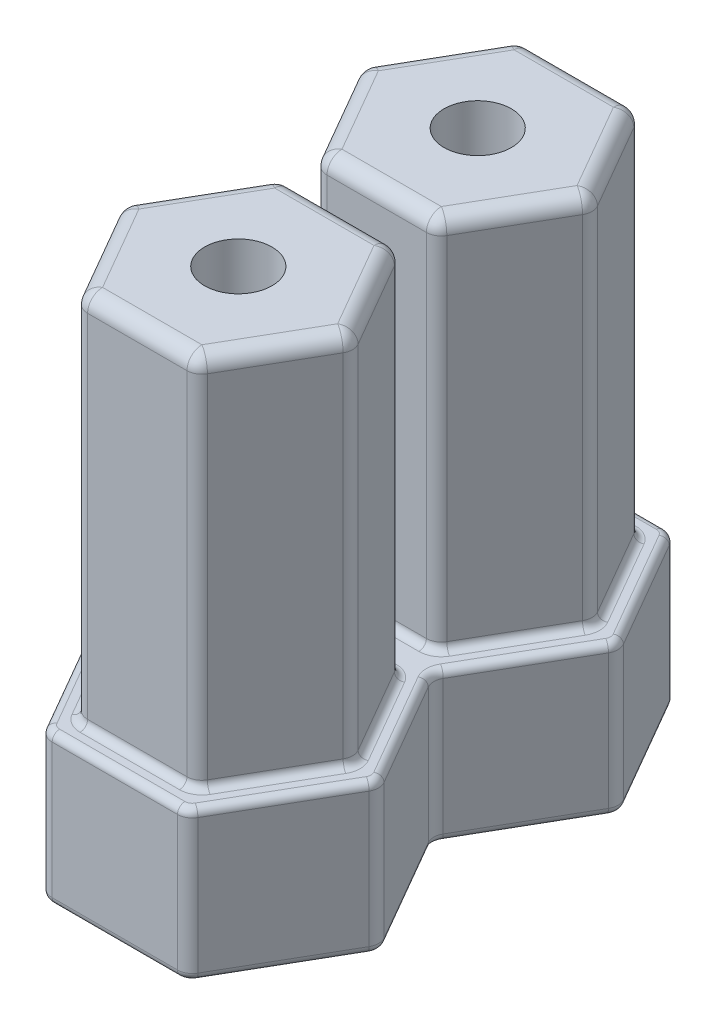
SolidWorks part; units mm, degrees
ref_plane "Front Plane" through (0, 0, 0) normal (0, 0, 1) x (1, 0, 0)
ref_plane "Top Plane" through (0, 0, 0) normal (0, 1, 0) x (1, 0, 0)
ref_plane "Right Plane" through (0, 0, 0) normal (1, 0, 0) x (0, 0, -1)
sketch "Sketch1" plane through (0, 0, 0) normal (0, 1, 0) x (1, 0, 0)
  line L0 (4.9075, 8) -> (9.5263, 16)
  line L1 (3.8971, -6.75) -> (7.7942, 0)
  line L2 (7.7942, 0) -> (3.8971, 6.75)
  line L3 (3.8971, 6.75) -> (-3.8971, 6.75)
  line L4 (-3.8971, 6.75) -> (-7.7942, 0)
  line L5 (-7.7942, 0) -> (-3.8971, -6.75)
  line L6 (-3.8971, -6.75) -> (3.8971, -6.75)
  line L7 (3.8971, 9.25) -> (7.7942, 16)
  line L8 (7.7942, 16) -> (3.8971, 22.75)
  line L9 (3.8971, 22.75) -> (-3.8971, 22.75)
  line L10 (-3.8971, 22.75) -> (-7.7942, 16)
  line L11 (-7.7942, 16) -> (-3.8971, 9.25)
  line L12 (-3.8971, 9.25) -> (3.8971, 9.25)
  line L13 (9.5263, 16) -> (4.7631, 24.25)
  line L14 (4.7631, 24.25) -> (-4.7631, 24.25)
  line L15 (-4.7631, 24.25) -> (-9.5263, 16)
  line L16 (-9.5263, 16) -> (-4.9075, 8)
  line L18 (4.7631, -8.25) -> (9.5263, 0)
  line L19 (9.5263, 0) -> (4.9075, 8)
  line L21 (-4.9075, 8) -> (-9.5263, 0)
  line L22 (-9.5263, 0) -> (-4.7631, -8.25)
  line L23 (-4.7631, -8.25) -> (4.7631, -8.25)
  line L24 (-4.7631, 8.25) -> (-9.5263, 0) construction
  line L25 (-9.5263, 16) -> (-4.7631, 7.75) construction
  line L26 (-4.7631, 7.75) -> (4.7631, 7.75) construction
  line L27 (4.7631, 8.25) -> (-4.7631, 8.25) construction
  line L28 (9.5263, 0) -> (4.7631, 8.25) construction
  line L29 (4.7631, 7.75) -> (9.5263, 16) construction
  circle A0 centre (0, 0) radius 6.75 construction
  circle A1 centre (0, 16) radius 6.75 construction
  dimension "D1" = 13.5
  dimension "D2" = 16
  dimension "D3" = 1.5
extrude "Boss-Extrude1" add sketch "Sketch1" along normal blind 25 contours L5 L6 L1 L2 L3 L4 | L11 L12 L7 L8 L9 L10 region at (0, 0, 0) region at (0, 0, -16)
extrude "Boss-Extrude2" add sketch "Sketch1<3>" against normal blind 10 contours L5 L6 L1 L2 L3 L4 | L22 L23 L18 L19 L0 L13 L14 L15 L16 L21 L6 L5 L4 L3 L2 L1 L12 L11 L10 L9 L8 L7 | L11 L12 L7 L8 L9 L10 region at (0, 0, -8) region at (0, 0, 0) region at (0, 0, -16)
sketch "Sketch1<3>" plane through (0, 0, 0) normal (0, 1, 0) x (1, 0, 0) same geometry as "Sketch1"
fillet "Fillet1" radius 1 34 edges at (-5.8457, 25, -3.375) (0, 25, -6.75) (5.8457, 25, -3.375) (5.8457, 25, 3.375) (0, 25, 6.75) (-5.8457, 25, 3.375) (-5.8457, 25, -19.375) (0, 25, -22.75) (5.8457, 25, -19.375) (5.8457, 25, -12.625) (0, 25, -9.25) (-5.8457, 25, -12.625) (4.7631, -5, 8.25) (9.5263, -5, 0) (4.9075, -5, -8) (9.5263, -5, -16) (4.7631, -5, -24.25) (-4.7631, -5, -24.25) (-9.5263, -5, -16) (-4.9075, -5, -8) (-9.5263, -5, 0) (-4.7631, -5, 8.25) (7.7942, 12.5, -16) (3.8971, 12.5, -22.75) (-3.8971, 12.5, -22.75) (-7.7942, 12.5, -16) (-3.8971, 12.5, -9.25) (3.8971, 12.5, -9.25) (3.8971, 12.5, -6.75) (-3.8971, 12.5, -6.75) (-7.7942, 12.5, 0) (-3.8971, 12.5, 6.75) (3.8971, 12.5, 6.75) (7.7942, 12.5, 0)
sketch "Sketch2" plane through (0, -10, 0) normal (0, -1, 0) x (1, 0, 0)
  point P0 (0, 0)
  point P1 (0, -16)
hole_wizard "CBORE for M4 Pan Head Screw1" positions "Sketch2" profile "Sketch3" counterbore size "M4" standard "ISO" end condition through all
sketch "Sketch3" plane through (0, -10, 0) normal (1, 0, 0) x (0, 0, -1)
  line L0 (0, 0) -> (0, 35)
  line L1 (0, 35) -> (2.25, 35)
  line L3 (2.25, 35) -> (2.25, 5)
  line L4 (2.25, 5) -> (4.5, 5)
  line L5 (4.5, 5) -> (4.5, 0)
  line L7 (4.5, 0) -> (0, 0)
  line L11 (0, -6.35) -> (0, 107.95) construction
  dimension "Thru Hole Dia." = 4.5
  dimension "Thru Hole Depth" = 35
  dimension "C'Bore Dia." = 9
  dimension "C'Bore Depth" = 5
fillet "Fillet2" radius 0.5 22 edges at (9.3716, -10, 0) (7.2169, -10, -4) (5.0622, -10, -8) (7.2169, -10, -12) (9.3716, -10, -16) (7.1447, -10, -20.125) (4.6858, -10, -24.116) (0, -10, -24.25) (-4.6858, -10, -24.116) (-7.1447, -10, -20.125) (-9.3716, -10, -16) (-7.2169, -10, -12) (-5.0622, -10, -8) (-7.2169, -10, -4) (-9.3716, -10, 0) (-7.1447, -10, 4.125) (-4.6858, -10, 8.116) (0, -10, 8.25) (4.6858, -10, 8.116) (7.1447, -10, 4.125) (0, -10, -20.5) (0, -10, -4.5)
fillet "Fillet3" radius 0.5 44 edges at (-3.8198, 0, -6.616) (0, 0, -6.75) (3.8198, 0, -6.616) (5.8457, 0, -3.375) (7.6395, 0, 0) (5.8457, 0, 3.375) (3.8198, 0, 6.616) (0, 0, 6.75) (-3.8198, 0, 6.616) (-5.8457, 0, 3.375) (-7.6395, 0, 0) (-7.6395, 0, -16) (-5.8457, 0, -19.375) (-3.8198, 0, -22.616) (0, 0, -22.75) (3.8198, 0, -22.616) (5.8457, 0, -19.375) (7.6395, 0, -16) (5.8457, 0, -12.625) (3.8198, 0, -9.384) (0, 0, -9.25) (-3.8198, 0, -9.384) (-5.8457, 0, -3.375) (-5.8457, 0, -12.625) (-4.6858, 0, 8.116) (-7.1447, 0, 4.125) (-9.3716, 0, 0) (-7.2169, 0, -4) (-5.0622, 0, -8) (-7.2169, 0, -12) (-9.3716, 0, -16) (-7.1447, 0, -20.125) (-4.6858, 0, -24.116) (0, 0, -24.25) (4.6858, 0, -24.116) (7.1447, 0, -20.125) (9.3716, 0, -16) (7.2169, 0, -12) (5.0622, 0, -8) (7.2169, 0, -4) (9.3716, 0, 0) (7.1447, 0, 4.125) (4.6858, 0, 8.116) (0, 0, 8.25)
